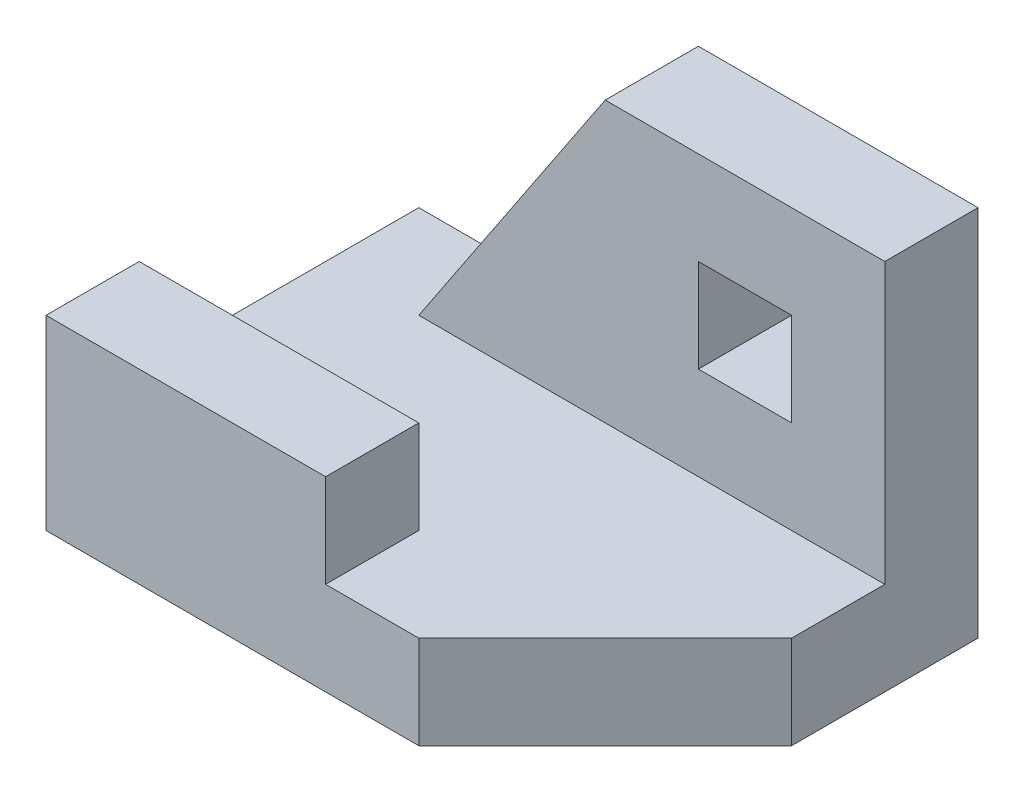
SolidWorks part; units mm, degrees
ref_plane "Front Plane" through (0, 0, 0) normal (0, 0, 1) x (1, 0, 0)
ref_plane "Top Plane" through (0, 0, 0) normal (0, 1, 0) x (1, 0, 0)
ref_plane "Right Plane" through (0, 0, 0) normal (1, 0, 0) x (0, 0, -1)
sketch "Sketch1" plane through (0, 0, 0) normal (0, 1, 0) x (1, 0, 0)
  line L0 (0, 0) -> (0, 1016)
  line L1 (0, 1016) -> (1524, 1016)
  line L2 (1524, 1016) -> (1524, 508)
  line L3 (1524, 508) -> (1016, 0)
  line L4 (1016, 0) -> (0, 0)
  line L5 (0, 254) -> (762, 254)
  line L6 (762, 254) -> (762, 0)
  line L7 (254, 1016) -> (254, 762)
  line L8 (254, 762) -> (1524, 762)
  dimension "D1" = 1016
  dimension "D2" = 762
  dimension "D3" = 1524
  dimension "D4" = 1270
  dimension "D5" = 254
  dimension "D6" = 45
  dimension "D7" = 254
extrude "Boss-Extrude1" add sketch "Sketch1" along normal blind 254 contours L8 L7 L1 L0 L5 L6 L4 L3 L2 region at (713.619, 0, -501.9524)
extrude "Boss-Extrude2" add sketch "Sketch1<3>" along normal blind 508 contours L6 L5 L0 L4 region at (381, 0, -127)
sketch "Sketch1<3>" plane through (0, 0, 0) normal (0, 1, 0) x (1, 0, 0) same geometry as "Sketch1"
extrude "Boss-Extrude3" add sketch "Sketch1<4>" along normal blind 1016 contours L7 L8 L2 L1 region at (889, 0, -889)
sketch "Sketch1<4>" plane through (0, 0, 0) normal (0, 1, 0) x (1, 0, 0) same geometry as "Sketch1"
sketch "Sketch2" plane through (0, 0, -762) normal (0, 0, 1) x (1, 0, 0)
  line L0 (254, 254) -> (762, 1016)
  line L1 (254, 1016) -> (1524, 1016) construction
  line L2 (762, 1016) -> (254, 1016)
  line L3 (254, 1016) -> (254, 254)
  line L4 (1016, 762) -> (1016, 508)
  line L5 (1016, 508) -> (1270, 508)
  line L6 (1270, 508) -> (1270, 762)
  line L7 (1270, 762) -> (1016, 762)
  line L8 (1524, 1016) -> (1524, 254) construction
  line L9 (254, 635) -> (1524, 635) construction
  dimension "D1" = 508
  dimension "D2" = 254
  dimension "D3" = 254
  dimension "D4" = 254
  dimension "D5" = 254
extrude "Cut-Extrude1" cut sketch "Sketch2" against normal blind 254
